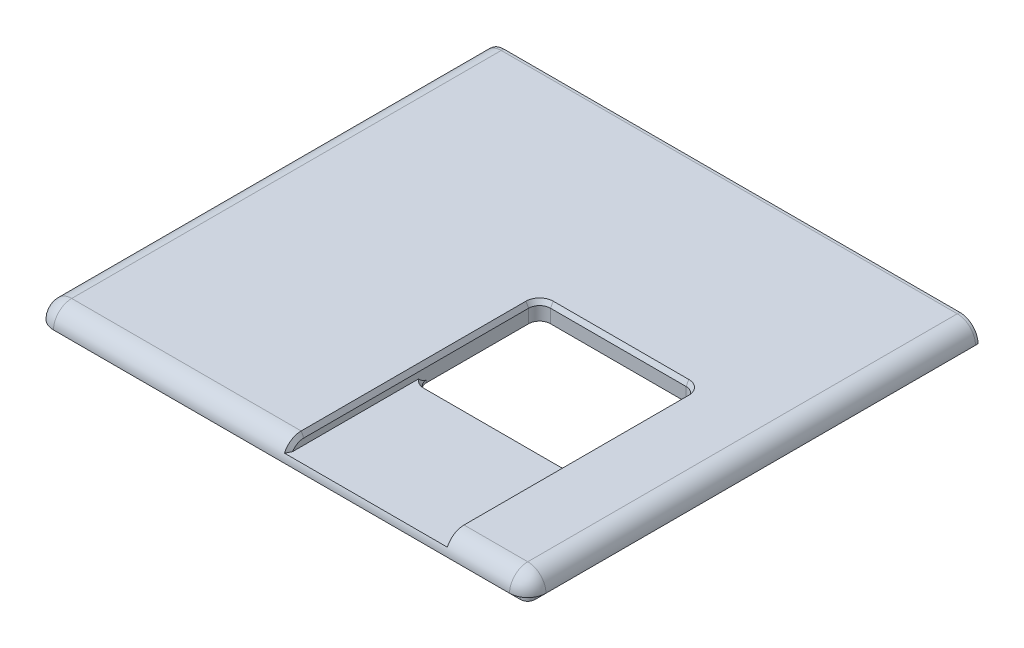
SolidWorks part; units mm, degrees
ref_plane "Front Plane" through (0, 0, 0) normal (0, 0, 1) x (1, 0, 0)
ref_plane "Top Plane" through (0, 0, 0) normal (0, 1, 0) x (1, 0, 0)
ref_plane "Right Plane" through (0, 0, 0) normal (1, 0, 0) x (0, 0, -1)
sketch "Sketch1" plane through (0, 0, 0) normal (0, 1, 0) x (1, 0, 0)
  line L0 (0, -4.4) -> (0, 4.4) construction
  line L1 (-67.645, 64) -> (67.645, 64)
  line L2 (-67.645, 64) -> (-67.645, -64)
  line L3 (-67.645, -64) -> (67.645, -64)
  line L4 (67.645, 64) -> (67.645, -64)
  line L5 (-4.4, 0) -> (4.4, 0) construction
  dimension "D1" = 67.645
  dimension "D2" = 67.645
  dimension "D3" = 64
  dimension "D4" = 64
extrude "Boss-Extrude1" add sketch "Sketch1" along normal blind 5
sketch "Sketch2" plane through (0, 0, 0) normal (0, -1, 0) x (1, 0, 0)
  line L0 (67.645, 64) -> (67.645, -64) construction
  line L1 (-64.645, 61) -> (64.645, 61)
  line L2 (-64.645, 61) -> (-64.645, -61)
  line L3 (-64.645, -61) -> (64.645, -61)
  line L4 (64.645, 61) -> (64.645, -61)
  line L5 (-67.645, 64) -> (67.645, 64) construction
  line L6 (-67.645, -64) -> (-67.645, 64) construction
  line L7 (67.645, -64) -> (-67.645, -64) construction
  dimension "D1" = 3
  dimension "D2" = 3
  dimension "D3" = 3
  dimension "D4" = 3
extrude "Boss-Extrude2" add sketch "Sketch2" along normal blind 3
fillet "Fillet4" radius 5 4 edges at (-67.645, 2.5, -64) (67.645, 2.5, -64) (67.645, 2.5, 64) (-67.645, 2.5, 64)
fillet "Fillet5" radius 5 8 edges at (-66.1805, 5, -62.5355) (-67.645, 5, 0) (-66.1805, 5, 62.5355) (0, 5, 64) (66.1805, 5, 62.5355) (67.645, 5, 0) (66.1805, 5, -62.5355) (0, 5, -64)
fillet "Fillet6" radius 2 4 edges at (64.645, -1.5, 61) (-64.645, -1.5, 61) (-64.645, -1.5, -61) (64.645, -1.5, -61)
sketch "Sketch3" plane through (0, 5, 0) normal (0, 1, 0) x (1, 0, 0)
  line L0 (-62.645, -59) -> (62.645, -59) construction
  line L2 (-67.645, 59) -> (-67.645, -59) construction
  line L3 (67.645, 59.75) -> (-67.645, 59.75)
  line L4 (67.645, 59.75) -> (67.645, 64)
  line L5 (67.645, 64) -> (-67.645, 64)
  line L6 (-67.645, 59.75) -> (-67.645, 64)
  line L7 (67.645, -59) -> (67.645, 59) construction
  line L8 (62.645, 64) -> (-62.645, 64) construction
  dimension "D1" = 118.75
extrude "Cut-Extrude1" cut sketch "Sketch3" against normal up to surface (8 mm away) up to face at (0, -3, 0)
sketch "Sketch4" plane through (0, -3, 0) normal (0, -1, 0) x (1, 0, 0)
  line L1 (-61.645, 58) -> (61.645, 58)
  line L2 (-61.645, 58) -> (-61.645, -59.75)
  line L3 (-61.645, -59.75) -> (61.645, -59.75)
  line L4 (61.645, 58) -> (61.645, -59.75)
  line L5 (-64.499, -59.75) -> (64.499, -59.75) construction
  line L6 (-64.645, 59) -> (-64.645, -59) construction
  line L7 (64.645, -59) -> (64.645, 59) construction
  line L8 (62.645, 61) -> (-62.645, 61) construction
  dimension "D1" = 3
  dimension "D2" = 3
  dimension "D3" = 3
extrude "Cut-Extrude2" cut sketch "Sketch4" against normal blind 3
fillet "Fillet7" radius 2 2 edges at (61.645, -1.5, 58) (-61.645, -1.5, 58)
sketch "Sketch5" plane through (0, 5, 0) normal (0, 1, 0) x (1, 0, 0)
  line L0 (-62.645, -64) -> (62.645, -64) construction
  line L1 (1.145, 5.75) -> (44.395, 5.75)
  line L2 (1.145, 5.75) -> (1.145, -64)
  line L3 (1.145, -64) -> (44.395, -64)
  line L4 (44.395, 5.75) -> (44.395, -64)
  line L5 (62.645, -59) -> (62.645, 59) construction
  line L6 (-62.645, 59) -> (-62.645, -59) construction
  line L7 (-62.645, 59.75) -> (62.645, 59.75) construction
  dimension "D1" = 18.25
  dimension "D2" = 63.79
  dimension "D3" = 54
extrude "Cut-Extrude3" cut sketch "Sketch5" against normal blind 3
sketch "Sketch6" plane through (0, 2, 0) normal (0, 1, 0) x (1, 0, 0)
  line L0 (44.395, -63.5826) -> (44.395, 5.75) construction
  line L1 (1.145, 5.75) -> (44.395, 5.75)
  line L2 (1.145, 5.75) -> (1.145, -28.25)
  line L3 (1.145, -28.25) -> (44.395, -28.25)
  line L4 (44.395, 5.75) -> (44.395, -28.25)
  dimension "D1" = 34
extrude "Cut-Extrude4" cut sketch "Sketch6" against normal up to surface (2 mm away) up to face at (0, 0, 18.2214)
fillet "Fillet9" radius 3 4 edges at (1.145, 1, 28.25) (44.395, 1, 28.25) (44.395, 2.5, -5.75) (1.145, 2.5, -5.75)
chamfer "Chamfer1" distance 0.75 angle 60 7 edges at (1.145, 4.1833, 61.7386) (44.395, 4.1833, 61.7386) (44.395, 5, 28.125) (43.5163, 5, -4.8713) (1.145, 5, 28.125) (2.0237, 5, -4.8713) (22.77, 5, -5.75) first distance on face at (11.385, 3.4297, 61.7664) first distance on face at (13.662, 5, 9.9757)
chamfer "Chamfer2" distance 0.75 angle 60 3 edges at (43.5163, 2, 27.3713) (2.0237, 2, 27.3713) (22.77, 2, 28.25) first distance on face at (22.8638, 2, 44.9545)
sketch "Sketch7" plane through (64.645, 0, 0) normal (1, 0, 0) x (0, 0, -1)
  line L0 (59, -3) -> (-59, -3) construction
  line L1 (6, -3) -> (32, -3)
  line L2 (6, -3) -> (6, 0)
  line L3 (6, 0) -> (32, 0)
  line L4 (32, -3) -> (32, 0)
  line L5 (-59, 0) -> (59, 0) construction
  line L6 (-59, 0) -> (-59, -3) construction
  line L7 (59.75, -3) -> (59.75, 0) construction
  dimension "D1" = 65
  dimension "D2" = 27.75
extrude "Cut-Extrude5" cut sketch "Sketch7" against normal up to surface (3 mm away) up to face at (61.645, -1.5, -1.875)
chamfer "Chamfer3" distance 0.75 angle 60 2 edges at (64.645, -1.5, -32) (64.645, -1.5, -6) first distance on face at (64.645, -1.5, -45.5) first distance on face at (64.645, -1.5, 26.5)
